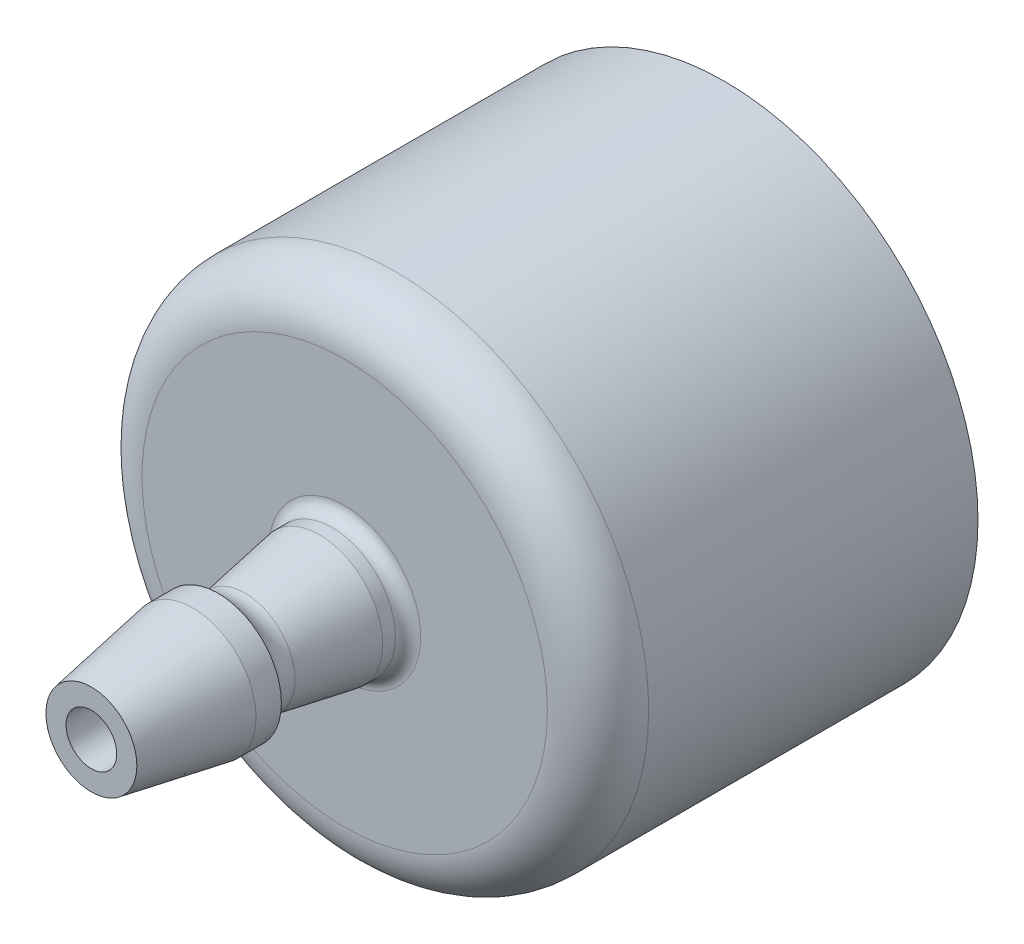
SolidWorks part; units mm, degrees
ref_plane "Front Plane" through (0, 0, 0) normal (0, 0, 1) x (1, 0, 0)
ref_plane "Top Plane" through (0, 0, 0) normal (0, 1, 0) x (1, 0, 0)
ref_plane "Right Plane" through (0, 0, 0) normal (1, 0, 0) x (0, 0, -1)
sketch "Sketch1" plane through (0, 0, 0) normal (0, 0, 1) x (1, 0, 0)
  circle A0 centre (0, 0) radius 2.5
  circle A1 centre (0, 0) radius 1
extrude "Boss-Extrude1" add sketch "Sketch1" along normal blind 5
chamfer "Chamfer2" distance 4 angle 10 1 edges at (2.5, 0, 5) first distance on face at (2.5, 0, 5)
ref_plane "Plane1" [suppressed] through (0, 0, 5) normal (0, 0, 1) x (1, 0, 0)
pattern_linear "LPattern2" count 2 spacing 5 along (0, 0, 1) of "Boss-Extrude1", "Chamfer2"
fillet "Fillet1" radius 1 1 edges at (1.7947, 0, 5)
sketch "Sketch2" plane through (0, 0, 0) normal (0, 0, 1) x (1, 0, 0)
  circle A0 centre (0, 0) radius 10
extrude "Boss-Extrude2" add sketch "Sketch2" against normal blind 15
sketch "Sketch3" plane through (0, 0, 0) normal (0, 0, 1) x (1, 0, 0)
  circle A0 centre (0, 0) radius 8
extrude "Cut-Extrude1" cut sketch "Sketch3" against normal blind 15 from offset 2 offset against normal yes
sketch "Sketch4" plane through (0, 0, 0) normal (0, 0, 1) x (1, 0, 0)
  circle A0 centre (0, 0) radius 1
extrude "Cut-Extrude2" cut sketch "Sketch4" against normal blind 15
fillet "Fillet2" radius 2 1 edges at (1, 0, -2)
fillet "Fillet3" radius 2 1 edges at (10, 0, 0)
fillet "Fillet4" radius 0.5 1 edges at (2.5, 0, 0)
fillet "Fillet5" radius 0.5 1 edges at (8, 0, -15)
